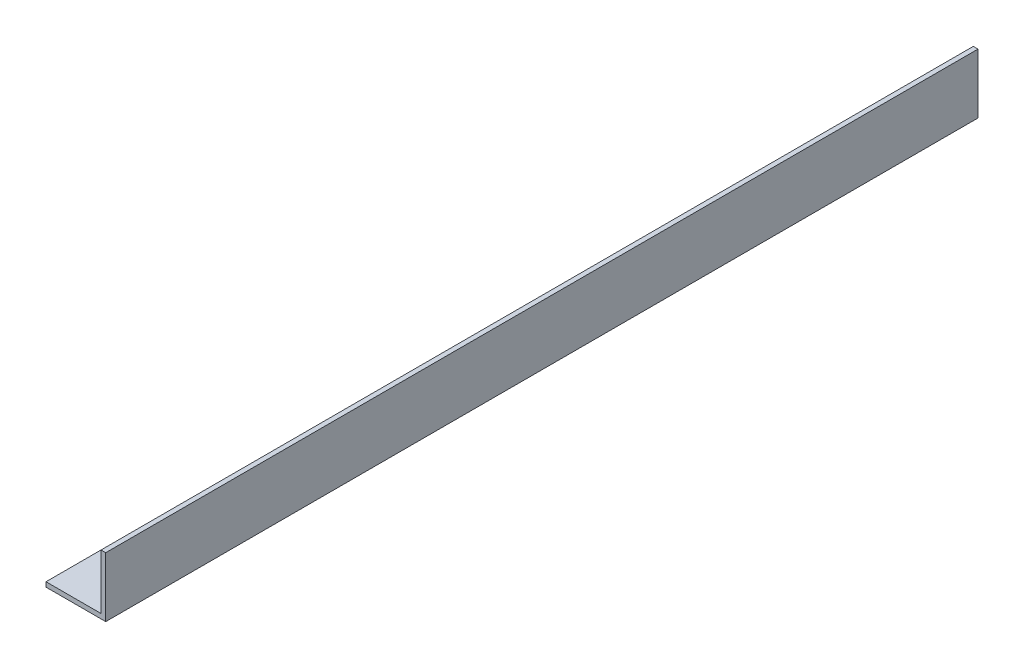
SolidWorks part; units mm, degrees
material "Acrylic (Medium-high impact)"
ref_plane "Front Plane" through (0, 0, 0) normal (0, 0, 1) x (1, 0, 0)
ref_plane "Top Plane" through (0, 0, 0) normal (0, 1, 0) x (1, 0, 0)
ref_plane "Right Plane" through (0, 0, 0) normal (1, 0, 0) x (0, 0, -1)
ref_axis "Axis1" through (0, -55, 0) along (0, 1, 0)
sketch "Sketch1" plane through (0, 0, 0) normal (0, 0, 1) x (1, 0, 0)
  line L0 (0, 25.4) -> (0, 0)
  line L1 (0, -55) -> (0, 55) construction
  line L2 (0, 0) -> (-25.4, 0)
  dimension "D1" = 25.4
  dimension "D2" = 25.4
extrude "Extrude-Thin1" add sketch "Sketch1" along normal blind 371 thin thin type one direction wall 2
